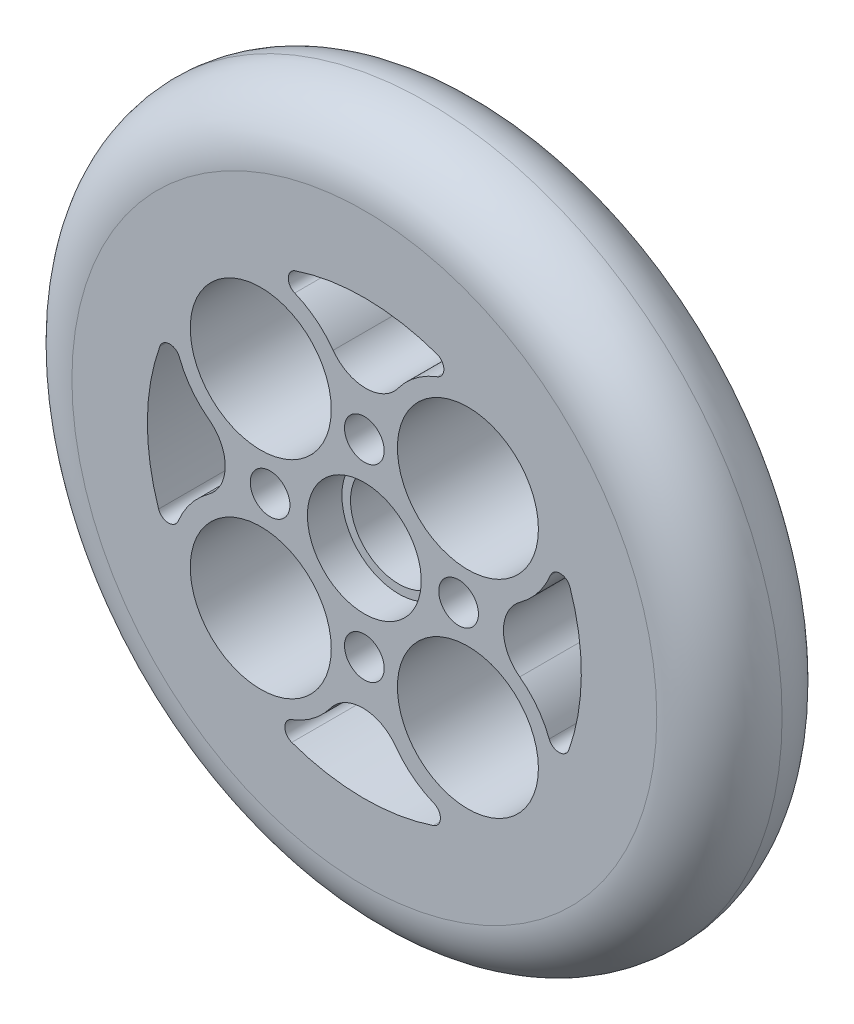
SolidWorks part; units mm, degrees
ref_plane "前视基准面" through (0, 0, 0) normal (0, 0, 1) x (1, 0, 0)
ref_plane "上视基准面" through (0, 0, 0) normal (0, 1, 0) x (1, 0, 0)
ref_plane "右视基准面" through (0, 0, 0) normal (1, 0, 0) x (0, 0, -1)
sketch "草图1" plane through (0, 0, 0) normal (0, 0, 1) x (1, 0, 0)
  circle A0 centre (0, 0) radius 68
  dimension "D1" = 136
extrude "凸台-拉伸2" add sketch "草图1" along normal blind 12 and the other way blind 12
fillet "圆角1" radius 12 2 edges at (68, 0, -12) (68, 0, 12)
sketch "草图2" plane through (0, 0, -12) normal (0, 0, -1) x (-1, 0, 0)
  circle A0 centre (0, 0) radius 9.25
  dimension "D1" = 18.5
extrude "切除-拉伸1" cut sketch "草图2" against normal through all
sketch "草图3" plane through (0, 0, -12) normal (0, 0, -1) x (-1, 0, 0)
  circle A0 centre (0, 0) radius 10.9
  dimension "D1" = 21.8
extrude "切除-拉伸2" cut sketch "草图3" against normal blind 6.6
mirror "镜向1" about plane through (0, 0, 0) normal (0, 0, 1) of "切除-拉伸2"
sketch "草图4" plane through (0, 0, 12) normal (0, 0, 1) x (1, 0, 0)
  line L0 (0, 0) -> (-97.0938, 0) construction
  line L1 (0, 0) -> (-70.3296, 70.3296) construction
  circle A0 centre (-18.05, 0) radius 3.8
  circle A1 centre (0, 18.05) radius 3.8
  circle A2 centre (18.05, 0) radius 3.8
  circle A3 centre (0, -18.05) radius 3.8
  circle A4 centre (-19.8343, 19.8343) radius 13.5
  circle A5 centre (19.8343, 19.8343) radius 13.5
  circle A6 centre (19.8343, -19.8343) radius 13.5
  circle A7 centre (-19.8343, -19.8343) radius 13.5
  dimension "D1" = 7.6
  dimension "D6" = 27
  dimension "D2" = 18.05
  dimension "D4" = 45
  dimension "D5" = 28.05
  dimension "D3" = 4
  dimension "D7" = 4
extrude "切除-拉伸3" cut sketch "草图4" against normal through all
sketch "草图5" plane through (0, 0, 12) normal (0, 0, 1) x (1, 0, 0)
  arc A0 (-39.1562, 13.8995) -> (-39.3954, -13.2061) centre (0, 0) ccw
  circle A1 centre (-19.8343, 19.8343) radius 13.5 construction
  circle A2 centre (-19.8343, 19.8343) radius 13.5
  arc A3 (-35.4011, 13.9388) -> (-29.7556, 6.4684) centre (-19.8343, 19.8343) ccw
  circle A4 centre (-19.8343, -19.8343) radius 13.5 construction
  circle A5 centre (-19.8343, -19.8343) radius 13.5
  arc A6 (-29.8397, -5.967) -> (-35.6494, -13.3311) centre (-19.8343, -19.8343) ccw
  circle A7 centre (-18.05, 0) radius 3.8 construction
  circle A8 centre (-18.05, 0) radius 3.8
  circle A9 centre (0, 0) radius 10.9 construction
  arc A10 (-35.4011, 13.9388) -> (-39.1562, 13.8995) centre (-37.2714, 13.2304) ccw
  arc A11 (-39.3954, -13.2061) -> (-35.6494, -13.3311) centre (-37.4992, -12.5704) ccw
  arc A12 (-29.7556, 6.4684) -> (-29.8397, -5.967) centre (-34.348, 0.2815) cw
  arc A13 (6.4684, 29.7556) -> (-5.967, 29.8397) centre (0.2815, 34.348) cw
  arc A14 (-5.967, 29.8397) -> (-13.3311, 35.6494) centre (-19.8343, 19.8343) ccw
  arc A15 (13.9388, 35.4011) -> (6.4684, 29.7556) centre (19.8343, 19.8343) ccw
  arc A16 (13.9388, 35.4011) -> (13.8995, 39.1562) centre (13.2304, 37.2714) ccw
  arc A17 (13.8995, 39.1562) -> (-13.2061, 39.3954) centre (0, 0) ccw
  arc A18 (-13.2061, 39.3954) -> (-13.3311, 35.6494) centre (-12.5704, 37.4992) ccw
  arc A19 (29.7556, -6.4684) -> (29.8397, 5.967) centre (34.348, -0.2815) cw
  arc A20 (29.8397, 5.967) -> (35.6494, 13.3311) centre (19.8343, 19.8343) ccw
  arc A21 (35.4011, -13.9388) -> (29.7556, -6.4684) centre (19.8343, -19.8343) ccw
  arc A22 (35.4011, -13.9388) -> (39.1562, -13.8995) centre (37.2714, -13.2304) ccw
  arc A23 (39.1562, -13.8995) -> (39.3954, 13.2061) centre (0, 0) ccw
  arc A24 (39.3954, 13.2061) -> (35.6494, 13.3311) centre (37.4992, 12.5704) ccw
  arc A25 (-6.4684, -29.7556) -> (5.967, -29.8397) centre (-0.2815, -34.348) cw
  arc A26 (5.967, -29.8397) -> (13.3311, -35.6494) centre (19.8343, -19.8343) ccw
  arc A27 (-13.9388, -35.4011) -> (-6.4684, -29.7556) centre (-19.8343, -19.8343) ccw
  arc A28 (-13.9388, -35.4011) -> (-13.8995, -39.1562) centre (-13.2304, -37.2714) ccw
  arc A29 (-13.8995, -39.1562) -> (13.2061, -39.3954) centre (0, 0) ccw
  arc A30 (13.2061, -39.3954) -> (13.3311, -35.6494) centre (12.5704, -37.4992) ccw
  dimension "D1" = 4
extrude "切除-拉伸4" cut sketch "草图5" against normal through all
